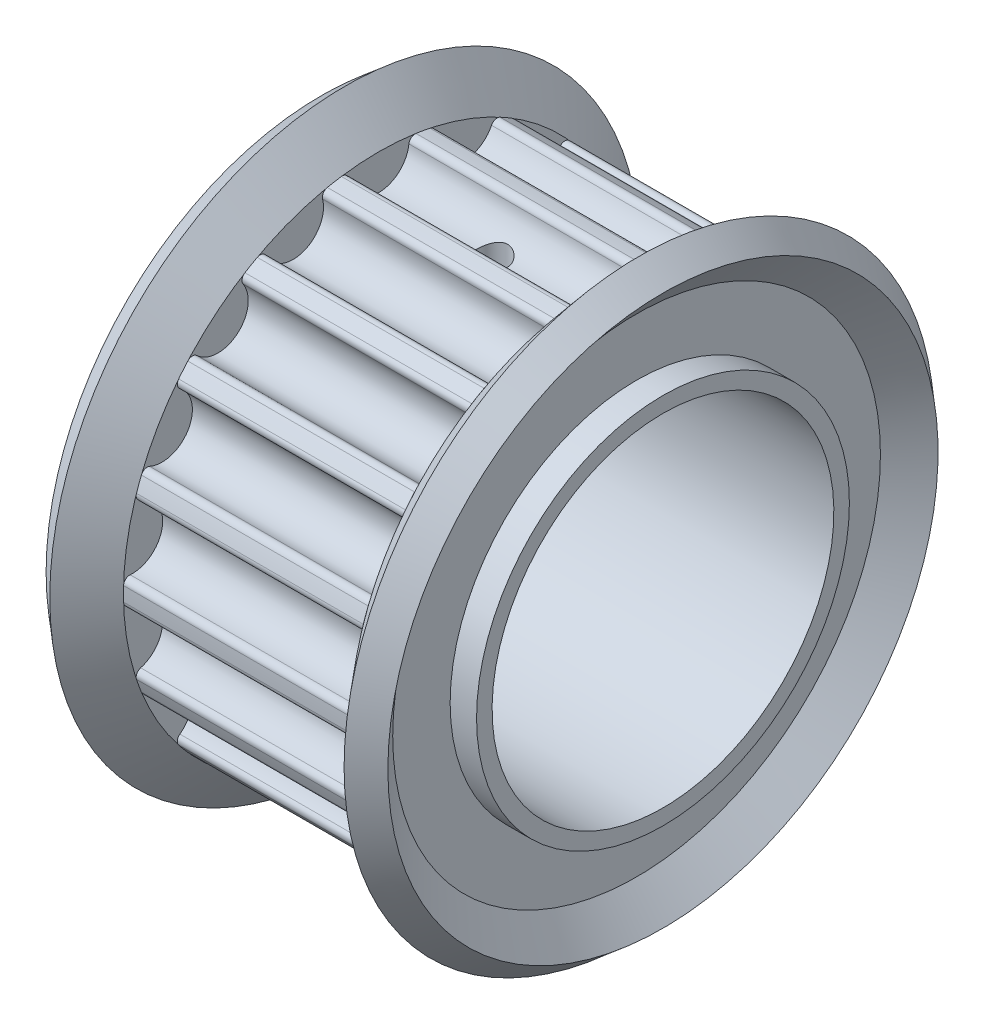
SolidWorks part; units mm, degrees
material "2014-T6"
ref_plane "Front Plane" through (0, 0, 0) normal (0, 0, 1) x (1, 0, 0)
ref_plane "Top Plane" through (0, 0, 0) normal (0, 1, 0) x (1, 0, 0)
ref_plane "Right Plane" through (0, 0, 0) normal (1, 0, 0) x (0, 0, -1)
sketch "Sketch1" plane through (0, 0, 0) normal (0, 0, 1) x (1, 0, 0)
  line L0 (-5.5, 4) -> (5.5, 4)
  line L1 (5.5, 4) -> (5.5, 6)
  line L2 (5.5, 6) -> (3.65, 6)
  line L3 (3.65, 6) -> (3.65, 8.215)
  line L4 (3.65, 8.215) -> (-3.65, 8.215)
  line L5 (-3.65, 8.215) -> (-3.65, 6)
  line L6 (-3.65, 6) -> (-5.5, 6)
  line L7 (-5.5, 6) -> (-5.5, 4)
  line L8 (0, 0) -> (0, 68.2564) construction
  line L9 (-16.0415, 0) -> (16.0415, 0) construction
  line L10 (-3.65, 8.595) -> (3.65, 8.595) construction
  dimension "D1" = 16.43
  dimension "D2" = 8
  dimension "D3" = 11
  dimension "D4" = 7.3
  dimension "D5" = 17.19
  dimension "D6" = 12
revolve "Revolve1" add sketch "Sketch1" angle 360 about L9
sketch "Sketch2" plane through (0, 0, 0) normal (1, 0, 0) x (0, 0, -1)
  line L0 (0, 7.075) -> (0, 8.215) construction
  line L1 (0, 8.215) -> (0, 8.595) construction
  line L3 (0, 0) -> (0, 68.2564) construction
  line L4 (1.2, 8.1269) -> (-1.2, 8.1269) construction
  circle A0 centre (0, 0) radius 8.595 construction
  arc A1 (1.2, 8.1269) -> (-1.2, 8.1269) centre (0, 0) ccw
  circle A2 centre (0, 0) radius 8.215 construction
  circle A3 centre (0, 0) radius 7.075 construction
  arc A4 (-0.9719, 7.95) -> (0.9719, 7.95) centre (0, 8.0523) ccw
  arc A5 (-1.2, 8.1269) -> (-0.9719, 7.95) centre (-1.1708, 7.929) cw
  arc A6 (1.2, 8.1269) -> (0.9719, 7.95) centre (1.1708, 7.929) ccw
  dimension "D2" = 0.2
  dimension "D1" = 1.14
  dimension "D3" = 2.4
extrude "Cut-Extrude1" cut sketch "Sketch2" against normal through all and the other way through all
pattern_circular "CirPattern1" count 18 over 360 about axis through (-16.0415, 0, 0) along (-1, 0, 0) of "Cut-Extrude1" reverse direction yes
sketch "Sketch3" plane through (0, 0, 0) normal (0, 0, 1) x (1, 0, 0)
  line L0 (3.65, 6) -> (4.65, 6)
  line L1 (3.65, 6) -> (3.65, 8.215)
  line L2 (3.65, 8.215) -> (4.7363, 9.5)
  line L3 (4.7363, 9.5) -> (5.5, 8.8544)
  line L4 (5.5, 8.8544) -> (4.65, 7.8489)
  line L5 (4.65, 7.8489) -> (4.65, 6)
  line L6 (0, 0) -> (16.0415, 0) construction
  line L7 (0, 0) -> (0, 11.7154) construction
  line L8 (0, 0) -> (0, 68.2564) construction
  line L9 (-3.65, 6) -> (-3.65, 8.215)
  line L10 (-3.65, 6) -> (-4.65, 6)
  line L11 (-4.65, 7.8489) -> (-4.65, 6)
  line L12 (-5.5, 8.8544) -> (-4.65, 7.8489)
  line L13 (-4.7363, 9.5) -> (-5.5, 8.8544)
  line L14 (-3.65, 8.215) -> (-4.7363, 9.5)
  dimension "D1" = 1.85
  dimension "D2" = 19
  dimension "D3" = 1
revolve "Revolve2" add sketch "Sketch3" angle 360 about L6
sketch "Sketch4" plane through (0, 0, 0) normal (0, 0, 1) x (1, 0, 0)
  line L0 (0, 0) -> (-15.4218, 0) construction
  line L1 (-5.5, 5.5) -> (5.5, 5.5)
  line L2 (-5.5, 5.5) -> (-5.5, 0)
  line L3 (-5.5, 0) -> (5.5, 0)
  line L4 (5.5, 5.5) -> (5.5, 0)
  line L5 (5.5, -4) -> (5.5, 4) construction
  line L6 (-5.5, 4) -> (-5.5, -4) construction
  dimension "D1" = 11
revolve "Cut-Revolve1" cut sketch "Sketch4" angle 360 about L0
sketch "Sketch5" plane through (0, 0, 0) normal (0, 1, 0) x (1, 0, 0)
  circle A0 centre (0, 0) radius 0.5
  dimension "D1" = 1
extrude "Cut-Extrude2" cut sketch "Sketch5" along normal through all
